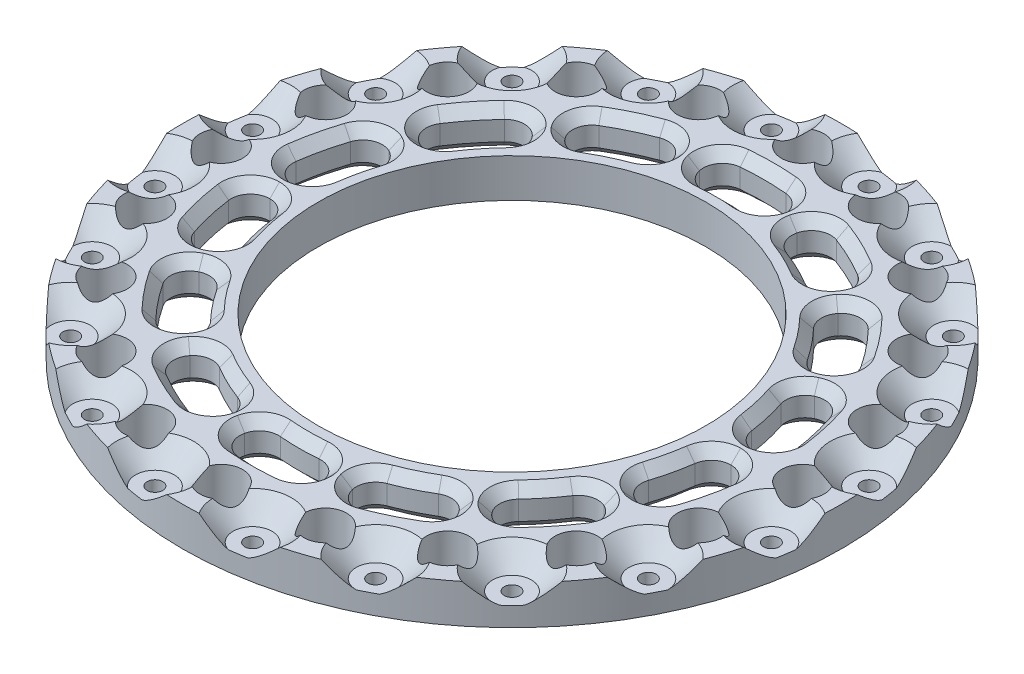
SolidWorks part; units mm, degrees
ref_plane "Front Plane" through (0, 0, 0) normal (0, 0, 1) x (1, 0, 0)
ref_plane "Top Plane" through (0, 0, 0) normal (0, 1, 0) x (1, 0, 0)
ref_plane "Right Plane" through (0, 0, 0) normal (1, 0, 0) x (0, 0, -1)
sketch "Sketch1" plane through (0, 0, 0) normal (0, 1, 0) x (1, 0, 0)
  line L0 (66.5, 0) -> (69.5, 0)
  line L1 (80.5, 0) -> (85, 0)
  circle A0 centre (0, 0) radius 75
  circle A1 centre (75, 0) radius 5.5
  circle A2 centre (71.3292, -23.1763) radius 5.5
  circle A3 centre (60.6763, -44.0839) radius 5.5
  circle A4 centre (44.0839, -60.6763) radius 5.5
  circle A5 centre (23.1763, -71.3292) radius 5.5
  circle A6 centre (0, -75) radius 5.5
  circle A7 centre (-23.1763, -71.3292) radius 5.5
  circle A8 centre (-44.0839, -60.6763) radius 5.5
  circle A9 centre (-60.6763, -44.0839) radius 5.5
  circle A10 centre (-71.3292, -23.1763) radius 5.5
  circle A11 centre (-75, 0) radius 5.5
  circle A12 centre (-71.3292, 23.1763) radius 5.5
  circle A13 centre (-60.6763, 44.0839) radius 5.5
  circle A14 centre (-44.0839, 60.6763) radius 5.5
  circle A15 centre (-23.1763, 71.3292) radius 5.5
  circle A16 centre (0, 75) radius 5.5
  circle A17 centre (23.1763, 71.3292) radius 5.5
  circle A18 centre (44.0839, 60.6763) radius 5.5
  circle A19 centre (60.6763, 44.0839) radius 5.5
  circle A20 centre (71.3292, 23.1763) radius 5.5
  circle A21 centre (0, 0) radius 66.5
  circle A22 centre (0, 0) radius 85
  circle A23 centre (0, 0) radius 50
  point P45 (0, 0)
  dimension "D1" = 20
extrude "Boss-Extrude1" add sketch "Sketch1" along normal blind 10
sketch "Sketch4" plane through (0, 10, 0) normal (0, 1, 0) x (1, 0, 0)
  circle A0 centre (0, 0) radius 50
  circle A1 centre (0, 0) radius 65
  circle A2 centre (0, 0) radius 55
extrude "Cut-Extrude2" cut sketch "Sketch4" against normal blind 10 contours A1 A2
sketch "Sketch5" plane through (0, 10, 0) normal (0, 1, 0) x (1, 0, 0)
  line L0 (-65, 0) -> (-55, 0)
  line L1 (-60, 0) -> (-60, 3)
  line L2 (-60, 0) -> (-60, -3)
  line L3 (-60, 3) -> (-54.9181, 3)
  line L4 (-60, 3) -> (-64.9307, 3)
  line L5 (-60, -3) -> (-54.9181, -3)
  line L6 (-60, -3) -> (-64.9307, -3)
  circle A0 centre (0, 0) radius 65 construction
  circle A1 centre (0, 0) radius 55 construction
  circle A3 centre (0, 0) radius 50
  circle A4 centre (0, 0) radius 65
  circle A5 centre (0, 0) radius 55
extrude "Boss-Extrude3" add sketch "Sketch5" against normal blind 10 contours A5 L0 L2 L5 | L6 L2 L0 A4 | L1 L4 A4 L0 | A5 L3 L1 L0
fillet "Fillet3" radius 5 4 edges at (-54.9181, 5, -3) (-64.9307, 5, -3) (-54.9181, 5, 3) (-64.9307, 5, 3)
pattern_circular "CirPattern2" count 14 over 360 about axis through (0, 0, 0) along (0, 1, 0) of "Boss-Extrude3", "Fillet3"
chamfer "Chamfer1" distance 2.5 angle 45 84 edges at (-23.8636, 10, -49.5533) (-28.2024, 10, -58.563) (-8.3697, 10, -55.7071) (-9.479, 10, -62.6906) (-16.6296, 10, -53.8219) (-18.6601, 10, -60.5951) (-43.0007, 10, -34.2919) (-50.819, 10, -40.5268) (-31.7113, 10, -46.5589) (-35.7408, 10, -52.3695) (-53.621, 10, 12.2387) (-38.3352, 10, -41.2765) (-43.1034, 10, -46.498) (-63.3703, 10, 14.4639) (-56.1729, 10, -4.2361) (-63.2281, 10, -4.7086) (-53.621, 10, -12.2387) (-63.3703, 10, -14.4639) (-48.772, 10, -28.1891) (-54.9236, 10, -31.676) (-56.1729, 10, 4.2361) (-52.448, 10, -20.5559) (-59.0096, 10, -23.1914) (-63.2281, 10, 4.7086) (-43.0007, 10, 34.2919) (-50.819, 10, 40.5268) (-52.448, 10, 20.5559) (-59.0096, 10, 23.1914) (-48.772, 10, 28.1891) (-54.9236, 10, 31.676) (-23.8636, 10, 49.5533) (-28.2024, 10, 58.563) (-38.3352, 10, 41.2765) (-43.1034, 10, 46.498) (-31.7113, 10, 46.5589) (-35.7408, 10, 52.3695) (0, 10, 55) (0, 10, 65) (-16.6296, 10, 53.8219) (-18.6601, 10, 60.5951) (-8.3697, 10, 55.7071) (-9.479, 10, 62.6906) (23.8636, 10, 49.5533) (28.2024, 10, 58.563) (8.3697, 10, 55.7071) (9.479, 10, 62.6906) (16.6296, 10, 53.8219) (18.6601, 10, 60.5951) (43.0007, 10, 34.2919) (50.819, 10, 40.5268) (31.7113, 10, 46.5589) (35.7408, 10, 52.3695) (38.3352, 10, 41.2765) (43.1034, 10, 46.498) (53.621, 10, 12.2387) (63.3703, 10, 14.4639) (48.772, 10, 28.1891) (54.9236, 10, 31.676) (52.448, 10, 20.5559) (59.0096, 10, 23.1914) (53.621, 10, -12.2387) (63.3703, 10, -14.4639) (56.1729, 10, 4.2361) (63.2281, 10, 4.7086) (56.1729, 10, -4.2361) (63.2281, 10, -4.7086) (43.0007, 10, -34.2919) (50.819, 10, -40.5268) (52.448, 10, -20.5559) (59.0096, 10, -23.1914) (48.772, 10, -28.1891) (54.9236, 10, -31.676) (23.8636, 10, -49.5533) (28.2024, 10, -58.563) (38.3352, 10, -41.2765) (43.1034, 10, -46.498) (31.7113, 10, -46.5589) (35.7408, 10, -52.3695) (0, 10, -55) (0, 10, -65) (16.6296, 10, -53.8219) (18.6601, 10, -60.5951) (8.3697, 10, -55.7071) (9.479, 10, -62.6906)
chamfer "Chamfer2" distance 2.5 angle 45 84 edges at (-23.8636, 0, -49.5533) (-28.2024, 0, -58.563) (-8.3697, 0, -55.7071) (-9.479, 0, -62.6906) (-16.6296, 0, -53.8219) (-18.6601, 0, -60.5951) (-43.0007, 0, -34.2919) (-50.819, 0, -40.5268) (-31.7113, 0, -46.5589) (-35.7408, 0, -52.3695) (-53.621, 0, 12.2387) (-38.3352, 0, -41.2765) (-43.1034, 0, -46.498) (-63.3703, 0, 14.4639) (-56.1729, 0, -4.2361) (-53.621, 0, -12.2387) (-63.3703, 0, -14.4639) (-48.772, 0, -28.1891) (-63.2281, 0, -4.7086) (-54.9236, 0, -31.676) (-52.448, 0, -20.5559) (-56.1729, 0, 4.2361) (-59.0096, 0, -23.1914) (-63.2281, 0, 4.7086) (-43.0007, 0, 34.2919) (-50.819, 0, 40.5268) (-52.448, 0, 20.5559) (-59.0096, 0, 23.1914) (-48.772, 0, 28.1891) (-54.9236, 0, 31.676) (-23.8636, 0, 49.5533) (-28.2024, 0, 58.563) (-38.3352, 0, 41.2765) (-43.1034, 0, 46.498) (-31.7113, 0, 46.5589) (-35.7408, 0, 52.3695) (0, 0, 55) (0, 0, 65) (-16.6296, 0, 53.8219) (-18.6601, 0, 60.5951) (-8.3697, 0, 55.7071) (-9.479, 0, 62.6906) (23.8636, 0, 49.5533) (28.2024, 0, 58.563) (8.3697, 0, 55.7071) (9.479, 0, 62.6906) (16.6296, 0, 53.8219) (18.6601, 0, 60.5951) (43.0007, 0, 34.2919) (50.819, 0, 40.5268) (31.7113, 0, 46.5589) (35.7408, 0, 52.3695) (38.3352, 0, 41.2765) (43.1034, 0, 46.498) (53.621, 0, 12.2387) (63.3703, 0, 14.4639) (48.772, 0, 28.1891) (54.9236, 0, 31.676) (52.448, 0, 20.5559) (59.0096, 0, 23.1914) (53.621, 0, -12.2387) (63.3703, 0, -14.4639) (56.1729, 0, 4.2361) (63.2281, 0, 4.7086) (56.1729, 0, -4.2361) (63.2281, 0, -4.7086) (43.0007, 0, -34.2919) (50.819, 0, -40.5268) (52.448, 0, -20.5559) (59.0096, 0, -23.1914) (48.772, 0, -28.1891) (54.9236, 0, -31.676) (23.8636, 0, -49.5533) (28.2024, 0, -58.563) (38.3352, 0, -41.2765) (43.1034, 0, -46.498) (31.7113, 0, -46.5589) (35.7408, 0, -52.3695) (0, 0, -55) (0, 0, -65) (16.6296, 0, -53.8219) (18.6601, 0, -60.5951) (8.3697, 0, -55.7071) (9.479, 0, -62.6906)
sketch "Sketch6" plane through (0, 10, 0) normal (0, 1, 0) x (1, 0, 0)
  line L0 (0, 0) -> (-75, 0)
  line L1 (0, 0) -> (-71.3292, 23.1763)
  line L2 (0, 0) -> (-113.084, 17.9108)
  circle A3 centre (0, 0) radius 80.5
  circle A4 centre (-79.5089, 12.593) radius 2
  circle A5 centre (-79.5089, 12.593) radius 5
  dimension "D1" = 9
extrude "Cut-Extrude3" cut sketch "Sketch6" against normal blind 10 contours L2 A4 A3 | L2 A4 A3 | A3 A4 L2 | A3 A4 L2
sketch "Sketch8" plane through (0, 10, 0) normal (0, 1, 0) x (1, 0, 0)
  circle A0 centre (-79.5089, 12.593) radius 5
extrude "Cut-Extrude4" cut sketch "Sketch8" against normal blind 5
chamfer "Chamfer3" distance 5 angle 45 1 edges at (-74.5705, 10, -11.8108)
pattern_circular "CirPattern3" count 20 over 360 about axis through (0, 0, 0) along (0, 1, 0) of "Chamfer3", "Cut-Extrude4", "Cut-Extrude3"
